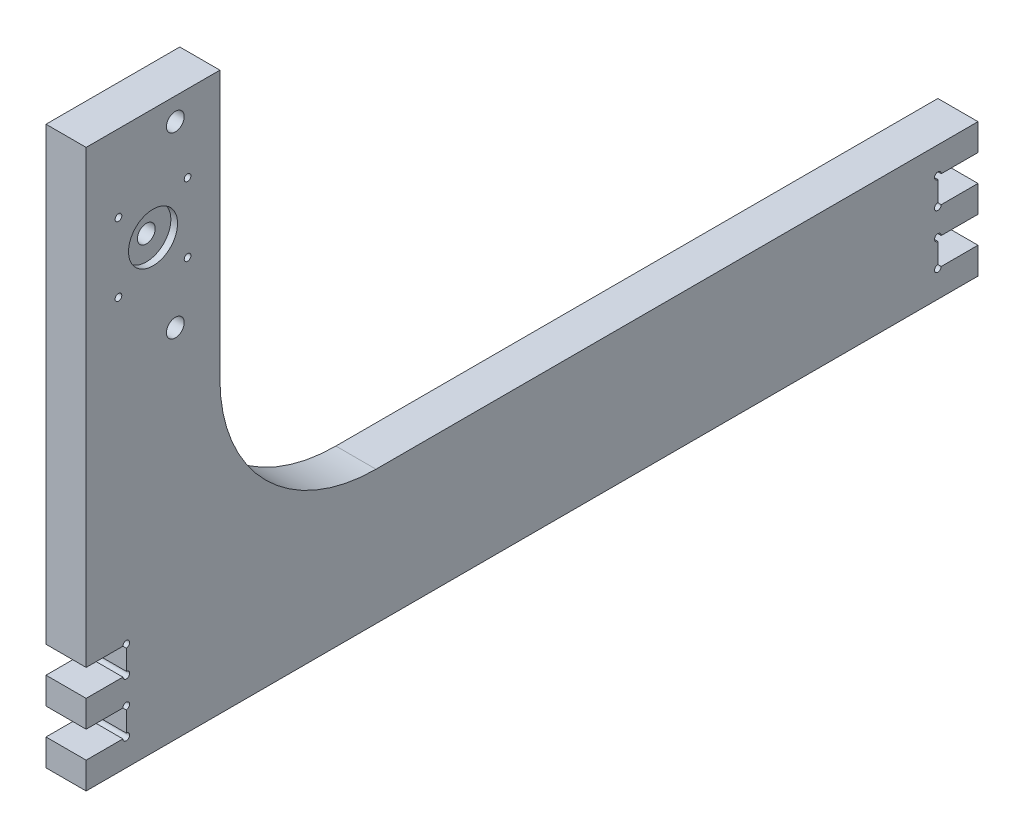
SolidWorks part; units mm, degrees
ref_plane "Front Plane" through (0, 0, 0) normal (0, 0, 1) x (1, 0, 0)
ref_plane "Top Plane" through (0, 0, 0) normal (0, 1, 0) x (1, 0, 0)
ref_plane "Right Plane" through (0, 0, 0) normal (1, 0, 0) x (0, 0, -1)
sketch "Sketch1" plane through (0, 0, 0) normal (1, 0, 0) x (0, 0, -1)
  line L0 (-1000, 0) -> (49000, 0) construction
  line L1 (-30, -250) -> (370, -250)
  line L2 (-30, -250) -> (-30, -238)
  line L4 (370, -250) -> (370, -238)
  line L6 (-30, -202) -> (-13.5, -202) construction
  line L7 (0, -1000) -> (0, 49000) construction
  line L9 (-30, 0) -> (-30, -202)
  line L10 (-30, -214) -> (-13.5, -214) construction
  line L11 (-30, -226) -> (-13.5, -226) construction
  line L12 (-30, -238) -> (-13.5, -238) construction
  line L13 (-12, -203.5) -> (-12, -212.5)
  line L14 (-30, -202) -> (-13.5, -202)
  line L15 (-30, -214) -> (-13.5, -214)
  line L16 (-30, -226) -> (-13.5, -226)
  line L17 (-13.5, -238) -> (-30, -238)
  line L19 (-30, -226) -> (-30, -214)
  line L20 (0, -750) -> (0, 49250) construction
  line L21 (-12, -227.5) -> (-12, -236.5)
  line L22 (353.5, -238) -> (370, -238)
  line L23 (352, -227.5) -> (352, -236.5)
  line L24 (370, -226) -> (353.5, -226)
  line L25 (370, -214) -> (353.5, -214)
  line L26 (352, -203.5) -> (352, -212.5)
  line L27 (370, -202) -> (353.5, -202)
  line L29 (370, -226) -> (370, -214)
  line L30 (370, -190) -> (370, -202)
  line L31 (30, 0) -> (30, -120)
  line L33 (100, -190) -> (370, -190)
  line L34 (-27.1942, -50) -> (27.1942, -50) construction
  line L35 (-30, -214) -> (-30, -226)
  line L36 (-30, -238) -> (-30, -250)
  line L37 (-30, 0) -> (30, 0)
  line L38 (10, -1000) -> (10, 49000) construction
  circle A1 centre (0, -50) radius 4
  circle A2 centre (10, -90) radius 4
  circle A3 centre (10, -10) radius 4
  circle A4 centre (15.5, -34.5) radius 1.5
  arc A5 (100, -190) -> (30, -120) centre (100, -120) cw
  circle A6 centre (-15.5, -34.5) radius 1.5
  circle A7 centre (15.5, -65.5) radius 1.5
  circle A8 centre (-15.5, -65.5) radius 1.5
  arc A9 (-12, -203.5) -> (-13.5, -202) centre (-12, -202) ccw
  arc A10 (-13.5, -214) -> (-12, -212.5) centre (-12, -214) ccw
  arc A11 (-12, -227.5) -> (-13.5, -226) centre (-12, -226) ccw
  arc A12 (-13.5, -238) -> (-12, -236.5) centre (-12, -238) ccw
  arc A13 (353.5, -202) -> (352, -203.5) centre (352, -202) ccw
  arc A14 (352, -212.5) -> (353.5, -214) centre (352, -214) ccw
  arc A15 (353.5, -226) -> (352, -227.5) centre (352, -226) ccw
  arc A16 (352, -236.5) -> (353.5, -238) centre (352, -238) ccw
  point P0 (0, 0)
  point P11 (370, -244)
  point P23 (0, 0)
  point P51 (0, -50)
  point P62 (0, 0)
  point P67 (0, 0)
  point P70 (0, 0)
  dimension "D7" = 48
  dimension "D14" = 8
  dimension "D16" = 50
  dimension "D18" = 3
  dimension "D10" = 70
  dimension "D23" = 3
  dimension "D29" = 3
  dimension "D3" = 18
  dimension "D4" = 60
  dimension "D5" = 12
  dimension "D6" = 400
  dimension "D8" = 250
  dimension "D9" = 60
  dimension "D11" = 18
  dimension "D12" = 40
  dimension "D13" = 70
  dimension "D15" = 10
  dimension "D17" = 40
  dimension "D19" = 15.5
  dimension "D20" = 15.5
  dimension "D21" = 100
  dimension "D22" = 120
  dimension "D25" = 18
  dimension "D26" = 12
  dimension "D27" = 36
  dimension "D28" = 9
  dimension "D24" = 4
  dimension "D30" = 4
extrude "Boss-Extrude1" add sketch "Sketch1" along normal blind 18
sketch "Sketch3" plane through (18, 0, 0) normal (1, 0, 0) x (0, 0, -1)
  circle A0 centre (0, -50) radius 11
  dimension "D1" = 22
extrude "Cut-Extrude1" cut sketch "Sketch3" against normal blind 3
sketch "Sketch4" plane through (18, 0, 0) normal (1, 0, 0) x (0, 0, -1)
  line L0 (370, -202) -> (352, -202)
  line L1 (352, -202) -> (352, -214)
  line L3 (370, -214) -> (352, -214)
  line L4 (370, -226) -> (352, -226)
  line L5 (370, -238) -> (352, -238)
  line L6 (352, -236.5) -> (352, -238)
  line L7 (352, -226) -> (352, -227.5)
  line L8 (170, -1250) -> (170, 48750) construction
  line L9 (-30, -250) -> (370, -250) construction
  line L10 (-12, -226) -> (-12, -227.5)
  line L11 (-12, -236.5) -> (-12, -238)
  line L12 (-30, -238) -> (-12, -238)
  line L13 (-30, -226) -> (-12, -226)
  line L14 (-30, -214) -> (-12, -214)
  line L15 (-12, -202) -> (-12, -214)
  line L16 (-30, -202) -> (-12, -202)
  arc A0 (353.5, -202) -> (352, -203.5) centre (352, -202) ccw
  arc A1 (352, -212.5) -> (353.5, -214) centre (352, -214) ccw
  arc A2 (353.5, -226) -> (352, -227.5) centre (352, -226) ccw
  arc A3 (352, -236.5) -> (353.5, -238) centre (352, -238) ccw
  arc A4 (-12, -236.5) -> (-13.5, -238) centre (-12, -238) cw
  arc A5 (-13.5, -226) -> (-12, -227.5) centre (-12, -226) cw
  arc A6 (-12, -212.5) -> (-13.5, -214) centre (-12, -214) cw
  arc A7 (-13.5, -202) -> (-12, -203.5) centre (-12, -202) cw
  point P26 (170, -250)
  dimension "D1" = 3
  dimension "D3" = 12
  dimension "D2" = 4
  dimension "D4" = 3
